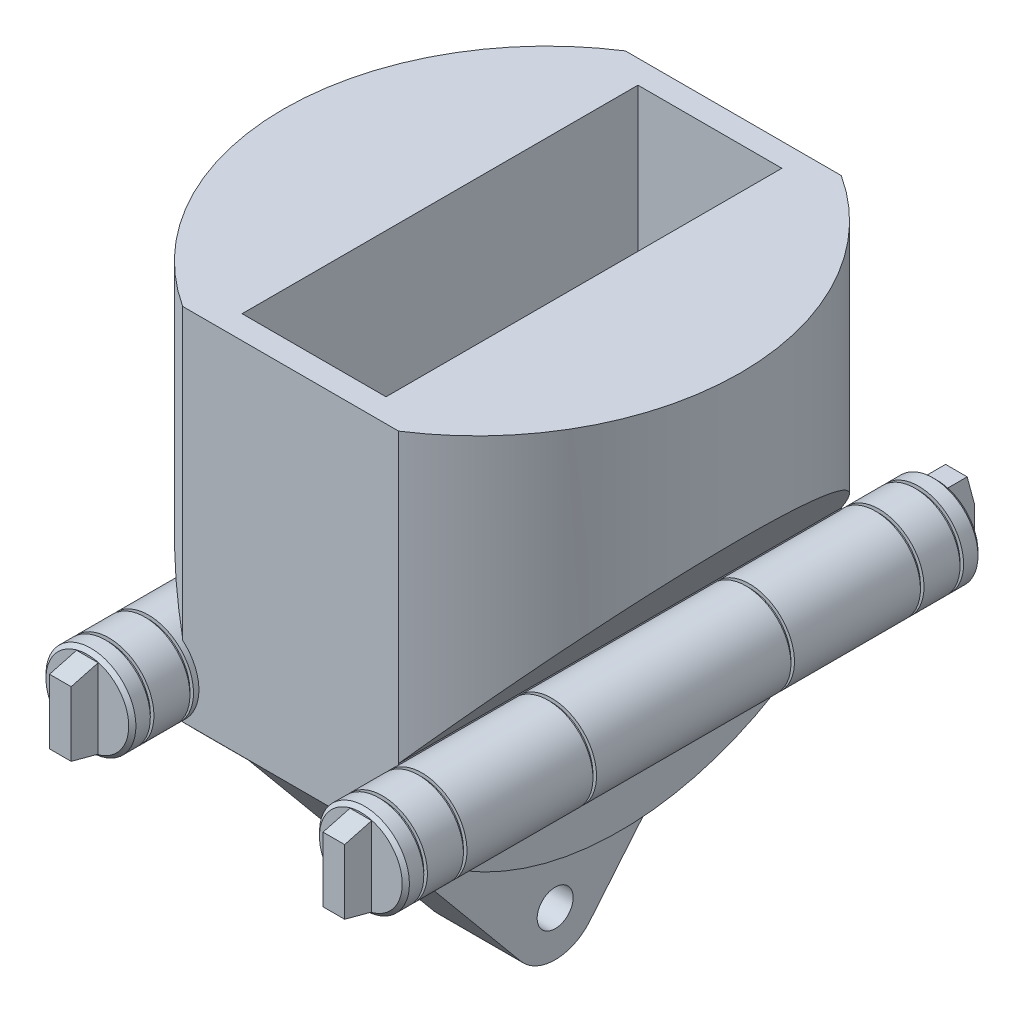
SolidWorks part; units mm, degrees
ref_plane "Front Plane" through (0, 0, 0) normal (0, 0, 1) x (1, 0, 0)
ref_plane "Top Plane" through (0, 0, 0) normal (0, 1, 0) x (1, 0, 0)
ref_plane "Right Plane" through (0, 0, 0) normal (1, 0, 0) x (0, 0, -1)
sketch "Sketch1" plane through (0, 0, 0) normal (1, 0, 0) x (0, 0, -1)
  line L1 (-61.5, 83.5) -> (61.5, 83.5)
  line L2 (-61.5, 83.5) -> (-61.5, -83.5)
  line L3 (-61.5, -83.5) -> (61.5, -83.5)
  line L4 (61.5, 83.5) -> (61.5, -83.5)
  line L5 (-61.5, 83.5) -> (61.5, -83.5) construction
  line L6 (-61.5, -83.5) -> (61.5, 83.5) construction
  point P0 (0, 0)
  dimension "D1" = 123
  dimension "D2" = 167
extrude "Boss-Extrude1" add sketch "Sketch1" along normal mid plane 127
sketch "Sketch2" plane through (0, 83.5, 0) normal (0, 1, 0) x (1, 0, 0)
  line L0 (0, 61.5) -> (0, -61.5) construction
  line L1 (63.5, 61.5) -> (-63.5, 61.5) construction
  line L2 (63.5, -61.5) -> (-63.5, -61.5) construction
  line L3 (-30, 61.5) -> (-30, -61.5) construction
  line L4 (-30, 61.5) -> (-63.5, 61.5)
  line L5 (-63.5, 61.5) -> (-63.5, -61.5)
  line L6 (-63.5, -61.5) -> (-30, -61.5)
  line L7 (63.5, -61.5) -> (30, -61.5)
  line L8 (30, 61.5) -> (63.5, 61.5)
  line L9 (63.5, 61.5) -> (63.5, -61.5)
  arc A0 (-30, 61.5) -> (-30, -61.5) centre (9.7015, 0) ccw
  arc A1 (30, 61.5) -> (30, -61.5) centre (-9.7015, 0) cw
  line M6 (-63.5, 61.5) -> (-63.5, -61.5)
  line M7 (-63.5, -61.5) -> (63.5, -61.5)
  line M8 (63.5, -61.5) -> (63.5, 61.5)
  line M9 (63.5, 61.5) -> (-63.5, 61.5)
  dimension "D2" = 73.2015
  dimension "D1" = 30
extrude "Cut-Extrude1" cut sketch "Sketch2" against normal through all contours A0 M9 M6 | A0 L5 M7 | A1 M8 M7 | A1 L9 M9 region at (-54.0203, 83.5, -46.9159) region at (-54.0203, 83.5, 46.9159) region at (54.0203, 83.5, -46.9159) region at (54.0203, 83.5, 46.9159)
sketch "Sketch3" plane through (0, 0, 61.5) normal (0, 0, 1) x (1, 0, 0)
  line L0 (0, 83.5) -> (0, -83.5) construction
  line L3 (30, 83.5) -> (-30, 83.5) construction
  line L4 (-12, -83.5) -> (-12, -43.5)
  line L5 (-12, -43.5) -> (-30, -43.5)
  line L6 (-30, -83.5) -> (-30, 83.5) construction
  line L7 (30, -83.5) -> (-30, -83.5) construction
  line L8 (-12, -83.5) -> (0, -83.5) construction
  line L9 (-30, -43.5) -> (-30, 3.5)
  line L10 (-30, 3.5) -> (-63.5, 43.5)
  line L11 (-63.5, 83.5) -> (-63.5, -83.5) construction
  line L12 (-63.5, 43.5) -> (-63.5, -83.5)
  line L13 (-63.5, -83.5) -> (-12, -83.5)
  line L14 (63.5, -83.5) -> (12, -83.5)
  line L15 (63.5, 43.5) -> (63.5, -83.5)
  line L16 (30, 3.5) -> (63.5, 43.5)
  line L17 (30, -43.5) -> (30, 3.5)
  line L18 (12, -43.5) -> (30, -43.5)
  line L19 (12, -83.5) -> (12, -43.5)
  dimension "D1" = 12
  dimension "D2" = 40
  dimension "D3" = 40
  dimension "D4" = 80
extrude "Cut-Extrude2" cut sketch "Sketch3" against normal through all
sketch "Sketch4" plane through (-30, 0, 0) normal (-1, 0, 0) x (0, 0, 1)
  line L0 (-61.5, -43.5) -> (-61.5, 3.5) construction
  line L1 (61.5, -43.5) -> (61.5, 3.5) construction
  line L2 (-61.5, -43.5) -> (61.5, -43.5) construction
  line L3 (-61.5, -16.5) -> (-61.5, -43.5)
  line L4 (-61.5, -43.5) -> (61.5, -43.5)
  line L5 (61.5, -43.5) -> (61.5, -16.5)
  arc A0 (-61.5, -16.5) -> (61.5, -16.5) centre (0, 40.0417) ccw
  point P9 (0, -43.5)
  line M1 (61.5, -43.5) -> (61.5, 3.5)
  line M3 (-61.5, 3.5) -> (-61.5, -43.5)
  line M4 (-61.5, -43.5) -> (61.5, -43.5)
  dimension "D1" = 20
extrude "Cut-Extrude3" cut sketch "Sketch4" against normal blind 18 contours A0 M3 M4 | A0 L4 M1 region at (-30, -35.6872, -46.6662) region at (-30, -35.6872, 46.6662)
mirror "Mirror1" about plane through (0, 0, 0) normal (1, 0, 0) of "Cut-Extrude3"
sketch "Sketch5" plane through (-12, 0, 0) normal (-1, 0, 0) x (0, 0, 1)
  line L0 (-61.5, -16.5) -> (-61.5, -83.5)
  line L1 (-61.5, -83.5) -> (61.5, -83.5)
  line L2 (61.5, -83.5) -> (61.5, -16.5)
  line L3 (0, -58.5) -> (0, -83.5) construction
  line L4 (-61.5, -16.5) -> (-9.617, -78.9852)
  line L5 (0, 0) -> (0, -71) construction
  line L6 (61.5, -16.5) -> (9.617, -78.9852)
  arc A0 (-9.617, -78.9852) -> (9.617, -78.9852) centre (0, -71) ccw
  circle A1 centre (0, -71) radius 5
  line M5 (61.5, -83.5) -> (61.5, -16.5)
  line M7 (-61.5, -16.5) -> (-61.5, -83.5)
  line M8 (-61.5, -83.5) -> (61.5, -83.5)
  dimension "D1" = 25
  dimension "D2" = 10
extrude "Cut-Extrude4" cut sketch "Sketch5" against normal through all contours A0 L4 M7 M8 | A0 L1 L6 M5 | A1 region at (-12, -61.2213, -42.8602) region at (-12, -61.2213, 42.8602) region at (-12, -71, 0)
sketch "Sketch6" plane through (0, 0, 0) normal (0, 0, 1) x (1, 0, 0)
  line L1 (30, 3.5) -> (30, 3.2345)
  line L2 (30, 3.5) -> (30, -16.5) construction
  line L6 (0, 83.5) -> (0, 0) construction
  line L7 (30, 83.5) -> (-30, 83.5) construction
  line L10 (-30, 3.5) -> (-30, 3.2345)
extrude "Boss-Extrude2" add sketch "Sketch6" along normal mid plane 40 separate body rebuild error yes
sketch "Sketch7" plane through (0, 0, 0) normal (0, 0, 1) x (1, 0, 0)
  circle A0 centre (38, -6.5) radius 12.5
  dimension "D1" = 25
extrude "Boss-Extrude3" add sketch "Sketch7" along normal mid plane 160
sketch "Sketch8" plane through (0, 0, 80) normal (0, 0, 1) x (1, 0, 0)
  line L1 (35, 4.5) -> (41, 4.5)
  line L2 (35, 4.5) -> (35, -17.5)
  line L3 (35, -17.5) -> (41, -17.5)
  line L4 (41, 4.5) -> (41, -17.5)
  line L5 (35, 4.5) -> (41, -17.5) construction
  line L6 (35, -17.5) -> (41, 4.5) construction
  point P0 (38, -6.5)
  dimension "D1" = 22
  dimension "D2" = 6
extrude "Boss-Extrude4" add sketch "Sketch8" along normal blind 7.5
ref_plane "Plane1" through (38, 0, 0) normal (1, 0, 0) x (0, 0, -1)
sketch "Sketch9" plane through (38, 0, 0) normal (1, 0, 0) x (0, 0, -1)
  line L0 (80, 6) -> (-80, 6) construction
  line L1 (-75, 6) -> (-74, 6)
  line L2 (-75, 6) -> (-75, 5)
  line L3 (-75, 5) -> (-74, 5)
  line L4 (-74, 6) -> (-74, 5)
  line L5 (-80, 6) -> (80, 6) construction
  line L6 (-64, 6) -> (-63, 6)
  line L7 (-64, 6) -> (-64, 5)
  line L8 (-64, 5) -> (-63, 5)
  line L9 (-63, 6) -> (-63, 5)
  line L10 (0, 6) -> (0, 0) construction
  line L11 (28, 5) -> (27, 5)
  line L12 (-28, 6) -> (-27, 6)
  line L13 (-28, 6) -> (-28, 5)
  line L14 (-28, 5) -> (-27, 5)
  line L15 (-27, 6) -> (-27, 5)
  line L16 (27, 6) -> (27, 5)
  line L17 (28, 6) -> (27, 6)
  line L18 (28, 6) -> (28, 5)
  line L19 (63, 6) -> (63, 5)
  line L20 (64, 6) -> (63, 6)
  line L21 (64, 5) -> (63, 5)
  line L22 (64, 6) -> (64, 5)
  line L23 (74, 6) -> (74, 5)
  line L24 (75, 6) -> (74, 6)
  line L25 (75, 6) -> (75, 5)
  line L26 (75, 5) -> (74, 5)
  line L27 (-80, -6.5) -> (80, -6.5) construction
  line L28 (-80, -17.5) -> (-80, 4.5) construction
  line L29 (80, -19) -> (80, 6) construction
  dimension "D1" = 1
  dimension "D2" = 10
  dimension "D3" = 5
  dimension "D4" = 35
revolve "Cut-Revolve1" cut sketch "Sketch9" angle 360 about L27
mirror "Mirror2" about plane through (0, 0, 0) normal (0, 0, 1) of "Boss-Extrude4"
chamfer "Chamfer1" distance 1 angle 45 2 edges at (50.5, -6.5, -80) (50.5, -6.5, 80)
chamfer "Chamfer2" distance 7.5 angle 15 4 edges at (38, -17.5, -87.5) (38, 4.5, -87.5) (38, -17.5, 87.5) (38, 4.5, 87.5) first distance on face at (38, -6.5, -87.5) first distance on face at (38, -17.5, 83.75) first distance on face at (38, 4.5, 83.75)
mirror "Mirror3" about plane through (0, 0, 0) normal (1, 0, 0) of "Cut-Revolve1", "Chamfer2", "Chamfer1", "Mirror2", "Boss-Extrude3", "Boss-Extrude4"
sketch "Sketch10" plane through (0, 83.5, 0) normal (0, 1, 0) x (1, 0, 0)
  line L1 (-20, 55) -> (20, 55)
  line L2 (-20, 55) -> (-20, -55)
  line L3 (-20, -55) -> (20, -55)
  line L4 (20, 55) -> (20, -55)
  line L5 (-20, 55) -> (20, -55) construction
  line L6 (-20, -55) -> (20, 55) construction
  point P0 (0, 0)
  dimension "D1" = 40
  dimension "D2" = 110
extrude "Boss-Extrude5" add sketch "Sketch10" along normal blind 30
scale "Scale1" bodies to scale 108 114 scale about centroid uniform scaling yes scale factor 0.333333
sketch "Sketch11" plane through (0, 58.6071, 0) normal (0, 1, 0) x (1, 0, 0)
  line L1 (-6.6667, 18.3332) -> (6.6667, 18.3332)
  line L2 (-6.6667, 18.3332) -> (-6.6667, -18.3335)
  line L3 (-6.6667, -18.3335) -> (6.6667, -18.3335)
  line L4 (6.6667, 18.3332) -> (6.6667, -18.3335)
extrude "Cut-Extrude5" cut sketch "Sketch11" against normal blind 30
